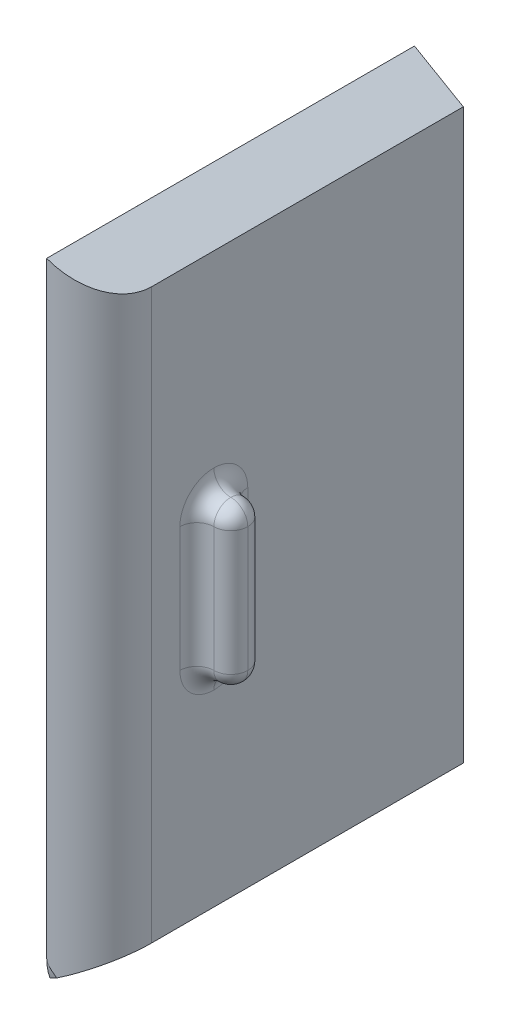
SolidWorks part; units mm, degrees
ref_plane "Front Plane" through (0, 0, 0) normal (0, 0, 1) x (1, 0, 0)
ref_plane "Top Plane" through (0, 0, 0) normal (0, 1, 0) x (1, 0, 0)
ref_plane "Right Plane" through (0, 0, 0) normal (1, 0, 0) x (0, 0, -1)
sketch "Sketch1" plane through (0, 0, 0) normal (0, 0, 1) x (1, 0, 0)
  line L4 (7.5184, 16.5597) -> (7.5184, -33.6682)
  line L6 (7.0777, -34.5) -> (3, -36.8542) construction
  line L7 (3, 19.7458) -> (3, -34.5) construction
  line L8 (3, 19.7458) -> (7.5184, 17.1371) construction
  line L9 (7.5184, -34.2455) -> (7.5184, 17.1371) construction
  line L13 (7.5184, -33.6682) -> (3.2, -36.1614)
  line L14 (3.2, -36.1614) -> (3.2, 19.0529)
  line L15 (3.2, 19.0529) -> (7.5184, 16.5597)
  dimension "D2" = 0.2
  dimension "D1" = 0.5
  dimension "D3" = 0.5
extrude "Boss-Extrude1" add sketch "Sketch1" against normal up to surface (32.5 mm away)
fillet "Fillet1" radius 5 1 edges at (7.5184, -8.5542, 0)
sketch "Sketch3" plane through (7.5184, 0, 0) normal (1, 0, 0) x (0, 0, -1)
  line L0 (32.5, -8.5542) -> (4.9533, -8.5542) construction
  line L1 (8.9533, -1.5542) -> (11.9533, -1.5542)
  line L2 (8.9533, -1.5542) -> (8.9533, -15.5542)
  line L3 (8.9533, -15.5542) -> (11.9533, -15.5542)
  line L4 (11.9533, -1.5542) -> (11.9533, -15.5542)
  line L5 (32.5, -33.6682) -> (32.5, 16.5597) construction
  line L6 (4.9533, 16.5597) -> (4.9533, -33.6682) construction
  point P10 (8.9533, -8.5542)
  dimension "D1" = 4
  dimension "D2" = 3
  dimension "D3" = 14
extrude "Boss-Extrude2" add sketch "Sketch3" along normal blind 3
fillet "Fillet2" radius 1.5 4 edges at (10.5184, -1.5542, -10.4533) (10.5184, -8.5542, -11.9533) (10.5184, -15.5542, -10.4533) (10.5184, -8.5542, -8.9533)
fillet "Fillet3" radius 1.5 6 edges at (7.5184, -8.5542, -8.9533) (7.5184, -8.5542, -11.9533) (10.0791, -15.1149, -9.3927) (10.0791, -15.1149, -11.514) (10.0791, -1.9936, -11.514) (10.0791, -1.9936, -9.3927)
sketch "Sketch4" plane through (3.2, 0, 0) normal (-1, 0, 0) x (0, 0, 1)
  line L0 (-32.5, -36.1614) -> (0, -36.1614) construction
  line L1 (-0.2841, -36.1614) -> (0, -36.1614)
  line L2 (0, -36.1614) -> (0, -34.5)
  arc A0 (0, -34.5) -> (-0.2841, -36.1614) centre (-5, -34.5) cw
  arc A1 (-0.6153, -36.8542) -> (-0.0232, -34.5) centre (-5, -34.5) ccw construction
extrude "Cut-Extrude1" cut sketch "Sketch4" against normal up to surface up to face at (5.8232, -8.5542, -2.0721)
